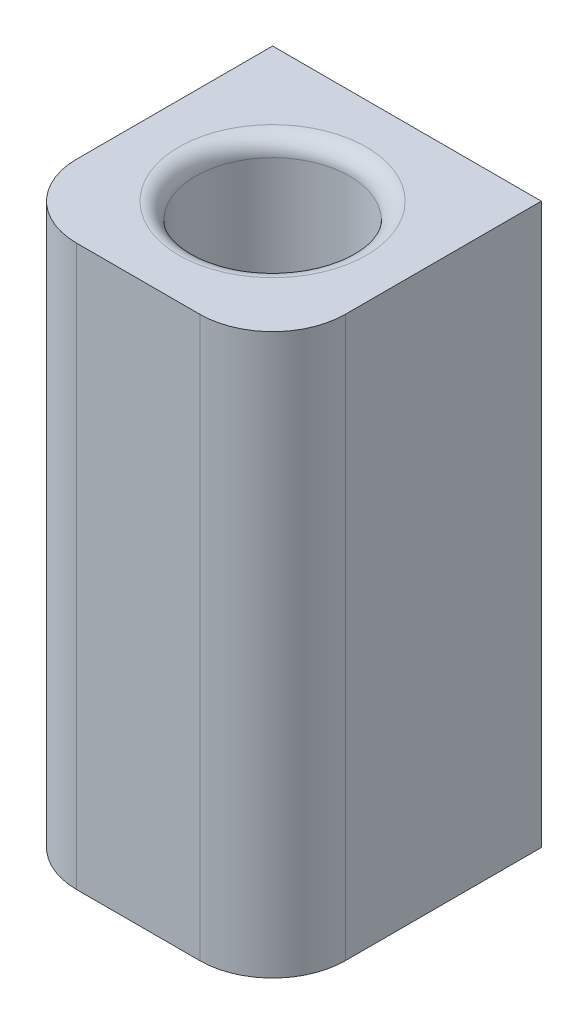
SolidWorks part; units mm, degrees
ref_plane "Front Plane" through (0, 0, 0) normal (0, 0, 1) x (1, 0, 0)
ref_plane "Top Plane" through (0, 0, 0) normal (0, 1, 0) x (1, 0, 0)
ref_plane "Right Plane" through (0, 0, 0) normal (1, 0, 0) x (0, 0, -1)
sketch "Sketch1" plane through (0, 0, 0) normal (0, 1, 0) x (1, 0, 0)
  line L0 (0, 29.8372) -> (-24, 29.8372)
  line L10 (24, 29.8372) -> (0, 29.8372)
  line L11 (-24, 29.8372) -> (-24, -18.1628)
  line L12 (-24, -18.1628) -> (24, -18.1628)
  line L13 (24, -18.1628) -> (24, 29.8372)
  line L14 (0, 29.8372) -> (0, 0) construction
  circle A0 centre (0, 5.8372) radius 13.75
  point P0 (0, 0)
  dimension "D1" = 27.5
  dimension "D2" = 24
  dimension "D3" = 24
  dimension "D4" = 24
  dimension "D5" = 24
extrude "Boss-Extrude1" add sketch "Sketch1" along normal blind 100
fillet "Fillet1" radius 13 2 edges at (-24, 50, 18.1628) (24, 50, 18.1628)
fillet "Fillet2" radius 3 2 edges at (0, 0, 7.9128) (0, 100, 7.9128)
